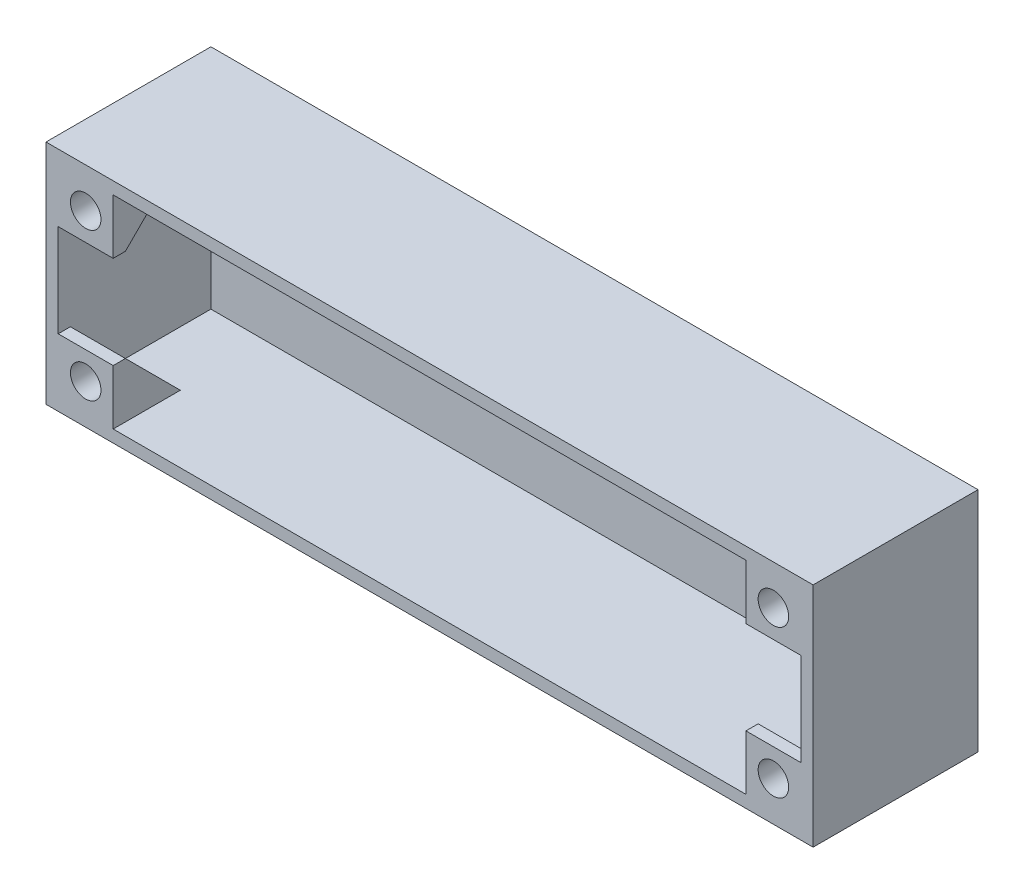
SolidWorks part; units mm, degrees
ref_plane "Front Plane" through (0, 0, 0) normal (0, 0, 1) x (1, 0, 0)
ref_plane "Top Plane" through (0, 0, 0) normal (0, 1, 0) x (1, 0, 0)
ref_plane "Right Plane" through (0, 0, 0) normal (1, 0, 0) x (0, 0, -1)
sketch "Sketch1" plane through (0, 0, -81.3977) normal (0, 0, -1) x (-1, 0, 0)
  line L0 (-95.4031, 76.5381) -> (-95.4031, 109.7381)
  line L1 (28.1969, 74.5381) -> (-97.4031, 74.5381)
  line L2 (28.1969, 74.5381) -> (28.1969, 111.7381)
  line L3 (28.1969, 111.7381) -> (-97.4031, 111.7381)
  line L4 (-97.4031, 74.5381) -> (-97.4031, 111.7381)
  line L5 (26.1969, 109.7381) -> (-95.4031, 109.7381)
  line L6 (26.1969, 76.5381) -> (26.1969, 109.7381)
  line L7 (26.1969, 76.5381) -> (-95.4031, 76.5381)
  dimension "D1" = 2
extrude "Boss-Extrude1" add sketch "Sketch1" along normal blind 25
sketch "Sketch2" plane through (0, 0, -106.3977) normal (0, 0, -1) x (-1, 0, 0)
  line L1 (-97.4031, 74.5381) -> (28.1969, 74.5381)
  line L2 (-97.4031, 74.5381) -> (-97.4031, 111.7381)
  line L3 (-97.4031, 111.7381) -> (28.1969, 111.7381)
  line L4 (28.1969, 74.5381) -> (28.1969, 111.7381)
extrude "Boss-Extrude2" add sketch "Sketch2" along normal blind 2
sketch "Sketch3" plane through (0, 0, -81.3977) normal (0, 0, 1) x (1, 0, 0)
  line L1 (95.4031, 109.7381) -> (86.4031, 109.7381)
  line L2 (95.4031, 109.7381) -> (95.4031, 100.7381)
  line L3 (95.4031, 100.7381) -> (86.4031, 100.7381)
  line L4 (86.4031, 109.7381) -> (86.4031, 100.7381)
  line L5 (95.4031, 76.5381) -> (86.4031, 76.5381)
  line L6 (95.4031, 76.5381) -> (95.4031, 85.5381)
  line L7 (95.4031, 85.5381) -> (86.4031, 85.5381)
  line L8 (86.4031, 76.5381) -> (86.4031, 85.5381)
  line L9 (-26.1969, 109.7381) -> (-17.1969, 109.7381)
  line L10 (-26.1969, 109.7381) -> (-26.1969, 100.7381)
  line L11 (-26.1969, 100.7381) -> (-17.1969, 100.7381)
  line L12 (-17.1969, 109.7381) -> (-17.1969, 100.7381)
  line L13 (-26.1969, 76.5381) -> (-17.1969, 76.5381)
  line L14 (-26.1969, 76.5381) -> (-26.1969, 85.5381)
  line L15 (-26.1969, 85.5381) -> (-17.1969, 85.5381)
  line L16 (-17.1969, 76.5381) -> (-17.1969, 85.5381)
  dimension "D1" = 9
  dimension "D2" = 9
  dimension "D3" = 9
  dimension "D4" = 9
  dimension "D5" = 9
  dimension "D6" = 9
  dimension "D7" = 9
  dimension "D8" = 9
extrude "Boss-Extrude3" add sketch "Sketch3" against normal blind 2
chamfer "Chamfer1" distance 9 angle 45 4 edges at (-21.6969, 76.5381, -83.3977) (90.9031, 76.5381, -83.3977) (90.9031, 109.7381, -83.3977) (-21.6969, 109.7381, -83.3977)
sketch "Sketch4" plane through (0, 0, -81.3977) normal (0, 0, 1) x (1, 0, 0)
  line L0 (-17.1969, 100.7381) -> (-17.1969, 109.7381) construction
  line L1 (-26.1969, 100.7381) -> (-17.1969, 100.7381) construction
  line L2 (-17.1969, 76.5381) -> (-17.1969, 85.5381) construction
  line L3 (-17.1969, 85.5381) -> (-26.1969, 85.5381) construction
  line L4 (95.4031, 85.5381) -> (86.4031, 85.5381) construction
  line L5 (86.4031, 85.5381) -> (86.4031, 76.5381) construction
  line L6 (86.4031, 100.7381) -> (95.4031, 100.7381) construction
  line L7 (86.4031, 109.7381) -> (86.4031, 100.7381) construction
  circle A0 centre (-21.6969, 105.2381) radius 2.5
  circle A1 centre (-21.6969, 81.0381) radius 2.5
  circle A2 centre (90.9031, 81.0381) radius 2.5
  circle A3 centre (90.9031, 105.2381) radius 2.5
  dimension "D1" = 5
  dimension "D2" = 5
  dimension "D3" = 5
  dimension "D4" = 5
  dimension "D5" = 4.5
  dimension "D6" = 4.5
  dimension "D7" = 4.5
  dimension "D8" = 4.5
  dimension "D9" = 4.5
  dimension "D10" = 4.5
  dimension "D11" = 4.5
  dimension "D12" = 4.5
extrude "Cut-Extrude1" cut sketch "Sketch4" against normal blind 15
